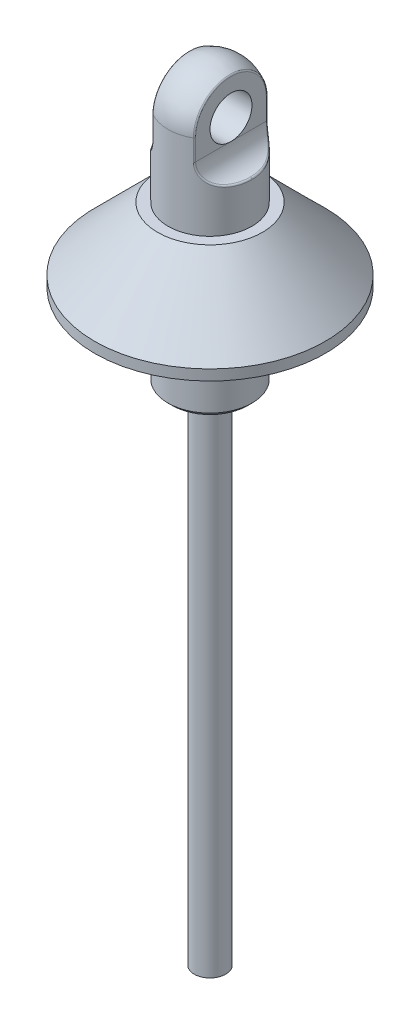
SolidWorks part; units mm, degrees
ref_plane "Front Plane" through (0, 0, 0) normal (0, 0, 1) x (1, 0, 0)
ref_plane "Top Plane" through (0, 0, 0) normal (0, 1, 0) x (1, 0, 0)
ref_plane "Right Plane" through (0, 0, 0) normal (1, 0, 0) x (0, 0, -1)
sketch "Sketch1" plane through (0, 0, 0) normal (0, 1, 0) x (1, 0, 0)
  circle A0 centre (0, 0) radius 34.925
  dimension "D1" = 69.85
extrude "Boss-Extrude1" add sketch "Sketch1" along normal blind 3.175
sketch "Sketch2" plane through (0, 3.175, 0) normal (0, 1, 0) x (1, 0, 0)
  circle A1 centre (0, 0) radius 34.925
  circle A2 centre (0, 0) radius 34.925
  dimension "D1" = 0
extrude "Boss-Extrude2" add sketch "Sketch2" along normal blind 19.05 draft 45
sketch "Sketch3" plane through (0, 22.225, 0) normal (0, 1, 0) x (1, 0, 0)
  circle A0 centre (0, 0) radius 12.7
  dimension "D1" = 25.4
extrude "Boss-Extrude3" add sketch "Sketch3" along normal blind 25.4
dome "Dome1" faces to dome 1 distance 12.7 reverse direction no elliptical dome no face at (0, 47.625, 12.7) parameters "D1"=12.7
ref_plane "Plane1" through (0, 63.5, 0) normal (0, 1, 0) x (1, 0, 0)
sketch "Sketch4" plane through (0, 63.5, 0) normal (0, 1, 0) x (1, 0, 0)
  line L0 (0, 12.7) -> (0, -12.7) construction
  line L1 (-6.35, -12.7) -> (-6.35, 12.7)
  line L2 (-6.35, 12.7) -> (-17.9694, 12.7)
  line L3 (-17.9694, 12.7) -> (-17.9694, -12.7)
  line L4 (-17.9694, -12.7) -> (-6.35, -12.7)
  line L5 (6.35, -12.7) -> (6.35, 12.7)
  line L6 (17.9694, -12.7) -> (6.35, -12.7)
  line L7 (17.9694, 12.7) -> (17.9694, -12.7)
  line L8 (6.35, 12.7) -> (17.9694, 12.7)
  circle A0 centre (0, 0) radius 12.7 construction
  dimension "D1" = 6.35
extrude "Cut-Extrude2" cut sketch "Sketch4" against normal blind 28.575
fillet "Fillet2" radius 6.35 2 edges at (6.35, 34.925, 0) (-6.35, 34.925, 0)
sketch "Sketch5" plane through (6.35, 0, 0) normal (1, 0, 0) x (0, 0, -1)
  circle A0 centre (0, 47.625) radius 6.35
  dimension "D1" = 12.7
extrude "Cut-Extrude3" cut sketch "Sketch5" against normal through all
fillet "Fillet3" radius 0.508 10 edges at (-6.35, 58.6235, 0) (-6.35, 44.45, -10.9985) (-8.9247, 36.1691, -9.0354) (-8.4466, 36.56, 9.4839) (8.9247, 36.1691, 9.0354) (8.4466, 36.56, -9.4839) (6.35, 44.45, -10.9985) (6.35, 58.6235, 0) (-6.35, 44.45, 10.9985) (6.35, 44.45, 10.9985)
sketch "Sketch6" plane through (0, 0, 0) normal (0, -1, 0) x (1, 0, 0)
  circle A0 centre (0, 0) radius 12.7
  dimension "D1" = 25.4
extrude "Boss-Extrude4" add sketch "Sketch6" along normal blind 25.4
chamfer "Chamfer1" distance 1.27 angle 45 1 edges at (0, -25.4, -12.7)
sketch "Sketch7" plane through (0, -25.4, 0) normal (0, -1, 0) x (1, 0, 0)
  circle A0 centre (0, 0) radius 4.7625
  dimension "D1" = 9.525
extrude "Boss-Extrude5" add sketch "Sketch7" along normal blind 152.4
